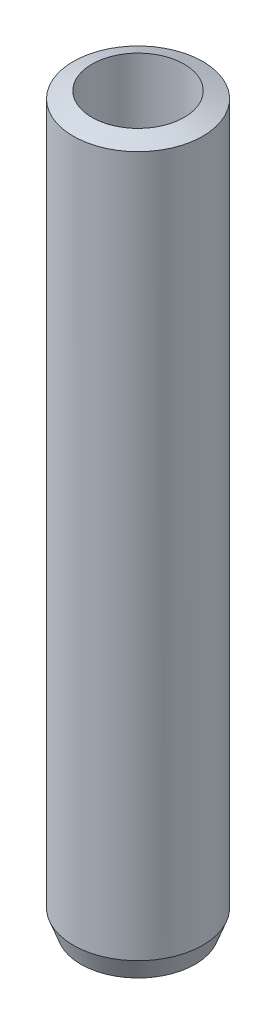
SolidWorks part; units mm, degrees
ref_plane "Front Plane" through (0, 0, 0) normal (0, 0, 1) x (1, 0, 0)
ref_plane "Top Plane" through (0, 0, 0) normal (0, 1, 0) x (1, 0, 0)
ref_plane "Right Plane" through (0, 0, 0) normal (1, 0, 0) x (0, 0, -1)
sketch "Sketch1" plane through (0, 0, 0) normal (0, 1, 0) x (1, 0, 0)
  circle A0 centre (0, 0) radius 50
  dimension "SHAFT_OD" = 100
extrude "Boss-Extrude1" add sketch "Sketch1" along normal blind 562.5177
sketch "Sketch2" plane through (0, 0, 0) normal (0, 1, 0) x (1, 0, 0)
  circle A0 centre (0, 0) radius 35.6215
  dimension "BORE_D" = 71.2431
extrude "Cut-Extrude1" cut sketch "Sketch2" along normal through all
chamfer "Chamfer1" distance 5.9011 angle 69.45 2 edges at (0, 562.5177, 50) (0, 0, 50) first distance on face at (0, 562.5177, 50) first distance on face at (0, 0, 35.6215)
